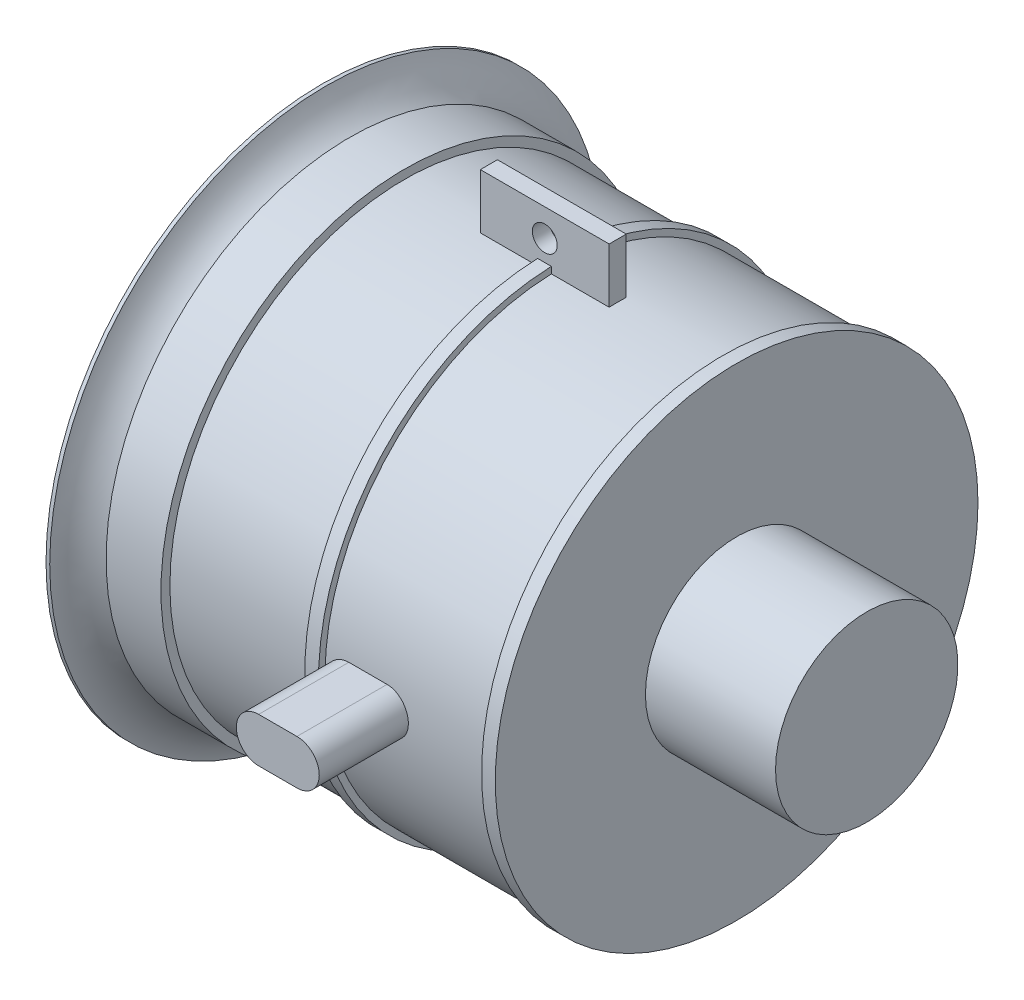
SolidWorks part; units mm, degrees
ref_plane "Front Plane" through (0, 0, 0) normal (0, 0, 1) x (1, 0, 0)
ref_plane "Top Plane" through (0, 0, 0) normal (0, 1, 0) x (1, 0, 0)
ref_plane "Right Plane" through (0, 0, 0) normal (1, 0, 0) x (0, 0, -1)
sketch "Sketch1" plane through (0, 0, 0) normal (1, 0, 0) x (0, 0, -1)
  circle A0 centre (0, 0) radius 43.3
  dimension "D1" = 86.6
extrude "Boss-Extrude1" add sketch "Sketch1" along normal blind 0.58
sketch "Sketch2" plane through (0.58, 0, 0) normal (1, 0, 0) x (0, 0, -1)
  circle A0 centre (0, 0) radius 36.83
  dimension "D1" = 73.66
extrude "Boss-Extrude2" add sketch "Sketch2" along normal blind 65 from surface starting at face at (0, 0, -43.3)
sketch "Sketch3" plane through (0, 0, 0) normal (0, 0, 1) x (1, 0, 0)
  line L0 (65, 36.83) -> (65, -36.83)
  line L1 (65, 36.83) -> (65, -36.83)
  line L2 (65, -36.83) -> (0.58, -36.83)
  line L3 (65, -36.83) -> (0.58, -36.83)
  line L4 (0.58, -36.83) -> (0.58, -43.3)
  line L5 (0.58, -36.83) -> (0.58, -43.3)
  line L6 (0.58, -43.3) -> (0, -43.3)
  line L7 (0.58, -43.3) -> (0, -43.3)
  line L8 (0, -43.3) -> (0, 43.3)
  line L9 (0, -43.3) -> (0, 43.3)
  line L10 (0, 43.3) -> (0.58, 43.3)
  line L11 (0, 43.3) -> (0.58, 43.3)
  line L12 (0.58, 43.3) -> (0.58, 36.83)
  line L13 (0.58, 43.3) -> (0.58, 36.83)
  line L14 (0.58, 36.83) -> (65, 36.83)
  line L15 (0.58, 36.83) -> (65, 36.83)
  line L16 (40.8507, 0) -> (46.8507, 0) construction
  line L17 (26.15, 36.83) -> (46.35, 36.83)
  line L18 (26.15, 36.83) -> (26.15, 45.4)
  line L19 (26.15, 45.4) -> (46.35, 45.4)
  line L20 (46.35, 36.83) -> (46.35, 45.4)
  line L21 (26.15, -36.83) -> (46.35, -36.83)
  line L22 (26.15, -36.83) -> (26.15, -45.4)
  line L23 (26.15, -45.4) -> (46.35, -45.4)
  line L24 (46.35, -36.83) -> (46.35, -45.4)
  line L25 (26.15, 45.4) -> (46.35, 45.4)
  line L26 (26.15, 45.4) -> (26.15, -45.4)
  line L27 (26.15, -45.4) -> (46.35, -45.4)
  line L28 (46.35, 45.4) -> (46.35, -45.4)
  line L29 (40.8507, 3.5) -> (46.8507, 3.5)
  line L30 (40.8507, -3.5) -> (46.8507, -3.5)
  circle A0 centre (36.25, 41.115) radius 1.95
  circle A1 centre (36.25, -41.115) radius 1.95
  arc A2 (40.8507, 3.5) -> (40.8507, -3.5) centre (40.8507, 0) ccw
  arc A3 (46.8507, -3.5) -> (46.8507, 3.5) centre (46.8507, 0) ccw
  point P20 (43.8507, 0)
  point P21 (36.25, 45.4)
  point P22 (46.35, 41.115)
  point P24 (26.15, -41.115)
  dimension "D4" = 3.9
  dimension "D1" = 18.65
  dimension "D2" = 20.2
  dimension "D3" = 90.8
  dimension "D5" = 7
  dimension "D6" = 6
extrude "Boss-Extrude3" add sketch "Sketch3" along normal blind 1.34 and the other way blind 1.34 contours L28 L15 L26 L3 | L15 L20 L19 L18 | L24 L3 L22 L23 region at (36.0102, 0, 0) region at (36.25, 37.0494, 0) region at (46.1306, -41.115, 0)
sketch "Sketch4" plane through (0.58, 0, 0) normal (1, 0, 0) x (0, 0, -1)
  circle A0 centre (0, 0) radius 37.85
  dimension "D1" = 75.7
extrude "Boss-Extrude4" add sketch "Sketch4" against normal blind 2.15 from surface starting at face at (65, 0, -36.83)
extrude "Boss-Extrude5" add sketch "Sketch4<2>" against normal blind 2.15 from offset 36.703
sketch "Sketch4<2>" plane through (0.58, 0, 0) normal (1, 0, 0) x (0, 0, -1) same geometry as "Sketch4"
sketch "Sketch5" plane through (65, 0, 0) normal (1, 0, 0) x (0, 0, -1)
  circle A0 centre (0, 0) radius 14.3
  dimension "D1" = 28.6
extrude "Boss-Extrude6" add sketch "Sketch5" along normal blind 85.4 from surface starting at face at (0, 0, -43.3)
extrude "Boss-Extrude7" add sketch "Sketch3<3>" along normal blind 50.8 contours L30 A3 L29 L28 | L29 A2 L30 L28 region at (48.0687, 0, 0) region at (42.1889, 0, 0)
sketch "Sketch3<3>" plane through (0, 0, 0) normal (0, 0, 1) x (1, 0, 0) same geometry as "Sketch3"
fillet "Fillet1" radius 8.89 1 edges at (0.58, 0, -36.83)
sketch "Sketch6" plane through (65, 0, 0) normal (1, 0, 0) x (0, 0, -1)
  circle A0 centre (0, 0) radius 38.227
  dimension "D1" = 76.454
extrude "Boss-Extrude8" add sketch "Sketch6" along normal blind 12.954 from surface starting at face at (0, 0, -43.3)
